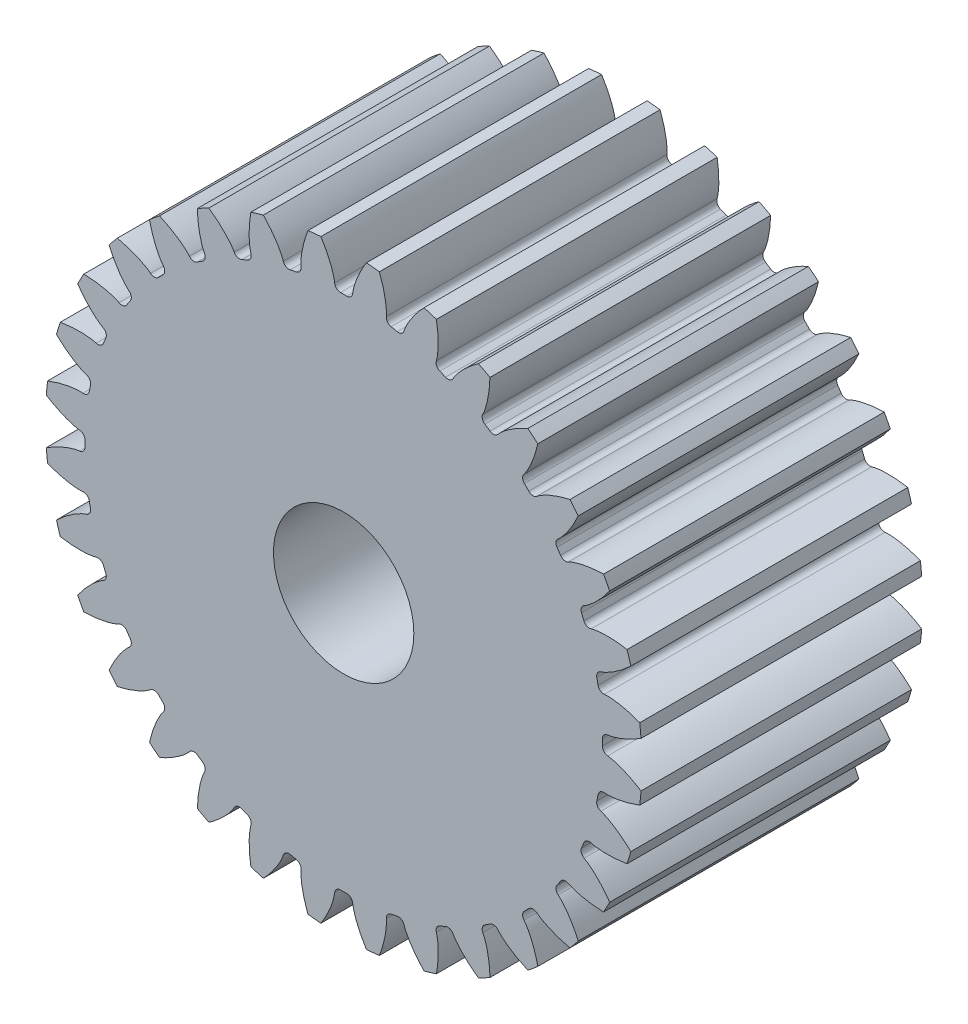
SolidWorks part; units mm, degrees
material "Plain Carbon Steel"
ref_plane "Front Plane" through (0, 0, 0) normal (0, 0, 1) x (1, 0, 0)
ref_plane "Top Plane" through (0, 0, 0) normal (0, 1, 0) x (1, 0, 0)
ref_plane "Right Plane" through (0, 0, 0) normal (1, 0, 0) x (0, 0, -1)
sketch "Sketch1" plane through (0, 0, 0) normal (0, 0, 1) x (1, 0, 0)
  line L0 (0, 0) -> (0, 12.7) construction
  line L1 (-4.0817, 14.1856) -> (4.0817, 11.2144) construction
  circle A0 centre (0, 0) radius 11.7078 construction
  circle A1 centre (0, 0) radius 13.4938 construction
  circle A2 centre (0, 0) radius 12.7 construction
  circle A3 centre (0, 0) radius 11.9341 construction
  point P8 (406.4, 0)
  point P13 (406.4, 0)
  dimension "OD | Outside Diameter" = 26.9875
  dimension "Root Diameter" = 23.4156
  dimension "Gear Pitch Diameter" = 25.4
  dimension "Base Diameter" = 23.8682
  dimension "Pressure Angle" = 20
  dimension "Number of Teeth" = 812.8
  dimension "Gear Pitch | Diametral Pitch" = 812.8
sketch "Sketch2" plane through (0, 0, 0) normal (1, 0, 0) x (0, 0, -1)
  line L0 (-6.35, 0) -> (6.35, 0) construction
  point P2 (7.1437, 0)
  point P5 (13.8906, 0)
  point P6 (-7.1437, 0)
  dimension "Length" = 12.7
  dimension "D1" = 13.4937
  dimension "D2" = 20.2406
  dimension "D3" = 13.4937
sketch "Sketch3" plane through (0, 0, 0) normal (0, 0, 1) x (1, 0, 0)
  circle A0 centre (0, 0) radius 13.4938
  circle A1 centre (0, 0) radius 13.4937 construction
extrude "Boss-Extrude1" add sketch "Sketch3" against normal up to vertex (6.35 mm away) and the other way up to vertex (6.35 mm away) up to point (0, 0, -6.35) other way up to point (0, 0, 6.35)
sketch "Sketch4" plane through (0, 0, 0) normal (0, 0, 1) x (1, 0, 0)
  line L0 (0, 0) -> (11.701, 0.4001) construction
  line L2 (0, 0) -> (11.701, -0.4001) construction
  line L4 (11.701, 0.4001) -> (11.9271, 0.4079)
  line L5 (11.9271, -0.4079) -> (11.701, -0.4001)
  arc A0 (11.701, 0.4001) -> (11.701, -0.4001) centre (0, 0) cw
  arc A3 (13.4545, 1.0288) -> (13.4545, -1.0288) centre (0, 0) cw
  circle A4 centre (0, 0) radius 13.4937 construction
  spline S0 degree 4 poles (11.9271, 0.4079) (11.9296, 0.408) (11.9365, 0.4084) (11.9495, 0.4095) (11.9706, 0.4117) (11.9976, 0.4153) (12.0324, 0.4207) (12.0733, 0.4281) (12.1181, 0.4373) (12.1668, 0.4485) (12.2153, 0.4607) (12.2636, 0.4738) (12.3116, 0.4878) (12.3697, 0.5057) (12.4391, 0.5286) (12.52, 0.5574) (12.6114, 0.5926) (12.7042, 0.631) (12.7953, 0.6709) (12.8869, 0.7137) (12.9752, 0.7568) (13.0666, 0.8041) (13.1507, 0.8491) (13.2444, 0.9022) (13.3199, 0.9459) (13.419, 1.0064) (13.4774, 1.0431) (13.5454, 1.087) (13.5756, 1.107) (13.5941, 1.1193) knots 0 0 0 0 0 0.005377 0.015084 0.028532 0.04661 0.064855 0.092111 0.119476 0.146842 0.174209 0.201575 0.228941 0.256307 0.307035 0.361767 0.4165 0.471232 0.525964 0.580697 0.635429 0.690161 0.744894 0.799626 0.854358 0.909091 0.954545 1 1 1 1 1 construction
  spline S1 degree 4 poles (11.9271, 0.4079) (11.9296, 0.408) (11.9365, 0.4084) (11.9495, 0.4095) (11.9706, 0.4117) (11.9976, 0.4153) (12.0324, 0.4207) (12.0733, 0.4281) (12.1181, 0.4373) (12.1668, 0.4485) (12.2153, 0.4607) (12.2636, 0.4738) (12.3116, 0.4878) (12.3697, 0.5057) (12.4391, 0.5286) (12.52, 0.5574) (12.6114, 0.5926) (12.7042, 0.631) (12.7953, 0.6709) (12.8869, 0.7137) (12.9752, 0.7568) (13.0666, 0.8041) (13.1507, 0.8491) (13.2444, 0.9022) (13.3199, 0.9459) (13.3975, 0.9933) (13.4352, 1.0167) (13.4545, 1.0288) knots 0 0 0 0 0 0.005377 0.015084 0.028532 0.04661 0.064855 0.092111 0.119476 0.146842 0.174209 0.201575 0.228941 0.256307 0.307035 0.361767 0.4165 0.471232 0.525964 0.580697 0.635429 0.690161 0.744894 0.799626 0.854358 0.909091 0.909091 0.909091 0.909091 0.909091
  spline S2 degree 4 poles (11.9271, -0.4079) (11.9296, -0.408) (11.9365, -0.4084) (11.9495, -0.4095) (11.9706, -0.4117) (11.9976, -0.4153) (12.0324, -0.4207) (12.0733, -0.4281) (12.1181, -0.4373) (12.1668, -0.4485) (12.2153, -0.4607) (12.2636, -0.4738) (12.3116, -0.4878) (12.3697, -0.5057) (12.4391, -0.5286) (12.52, -0.5574) (12.6114, -0.5926) (12.7042, -0.631) (12.7953, -0.6709) (12.8869, -0.7137) (12.9752, -0.7568) (13.0666, -0.8041) (13.1507, -0.8491) (13.2444, -0.9022) (13.3199, -0.9459) (13.419, -1.0064) (13.4774, -1.0431) (13.5454, -1.087) (13.5756, -1.107) (13.5941, -1.1193) knots 0 0 0 0 0 0.005377 0.015084 0.028532 0.04661 0.064855 0.092111 0.119476 0.146842 0.174209 0.201575 0.228941 0.256307 0.307035 0.361767 0.4165 0.471232 0.525964 0.580697 0.635429 0.690161 0.744894 0.799626 0.854358 0.909091 0.954545 1 1 1 1 1 construction
  spline S3 degree 4 poles (11.9271, -0.4079) (11.9296, -0.408) (11.9365, -0.4084) (11.9495, -0.4095) (11.9706, -0.4117) (11.9976, -0.4153) (12.0324, -0.4207) (12.0733, -0.4281) (12.1181, -0.4373) (12.1668, -0.4485) (12.2153, -0.4607) (12.2636, -0.4738) (12.3116, -0.4878) (12.3697, -0.5057) (12.4391, -0.5286) (12.52, -0.5574) (12.6114, -0.5926) (12.7042, -0.631) (12.7953, -0.6709) (12.8869, -0.7137) (12.9752, -0.7568) (13.0666, -0.8041) (13.1507, -0.8491) (13.2444, -0.9022) (13.3199, -0.9459) (13.3975, -0.9933) (13.4352, -1.0167) (13.4545, -1.0288) knots 0 0 0 0 0 0.005377 0.015084 0.028532 0.04661 0.064855 0.092111 0.119476 0.146842 0.174209 0.201575 0.228941 0.256307 0.307035 0.361767 0.4165 0.471232 0.525964 0.580697 0.635429 0.690161 0.744894 0.799626 0.854358 0.909091 0.909091 0.909091 0.909091 0.909091
  dimension "D1" = 23.4156
extrude "Cut-Extrude1" cut sketch "Sketch4" against normal through all both and the other way through all
fillet "Fillet1" radius 0.2663 2 edges at (11.701, -0.4001, 0) (11.701, 0.4001, 0)
pattern_circular "CirPattern1" count 32 over 360 about axis through (0, 0, 6.35) along (0, 0, -1) of "Cut-Extrude1", "Fillet1"
sketch "Sketch5" plane through (0, 0, 6.35) normal (0, 0, 1) x (1, 0, 0)
  point P0 (0, 0)
hole_wizard "1/4 (0.2500) Dowel Hole1" positions "Sketch5" profile "Sketch6" hole size "1/4" standard "ANSI Inch" end condition through all
sketch "Sketch6" plane through (0, 0, 6.35) normal (1, 0, 0) x (0, -1, 0)
  line L0 (0, 0) -> (0, 12.7)
  line L1 (0, 12.7) -> (3.175, 12.7)
  line L2 (3.175, 12.7) -> (3.175, 0)
  line L5 (3.175, 0) -> (0, 0)
  line L11 (0, -6.35) -> (0, 107.95) construction
  dimension "Thru Hole Dia." = 6.35
  dimension "Thru Hole Depth" = 12.7
equation "\"Root Diameter@Sketch1\"=\"Root Diameter\""
equation "\"OD | Outside Diameter@Sketch1\"=\"Outside Diameter\""
equation "\"D1@CirPattern1\"=\"Number of Teeth\""
equation "\"Diametral Pitch\"=32"
equation "\"Number of Teeth\"= 32"
equation "\"Pressure Angle\"=20"
equation "\"Pitch Diameter\"= \"Number of Teeth\" / \"Diametral Pitch\""
equation "\"Base Diameter\"= \"Pitch Diameter\" * cos ( \"Pressure Angle\" )"
equation "\"Outside Diameter\"= ( \"Number of Teeth\" + 2 ) / \"Diametral Pitch\""
equation "\"Dedendum\"= 1.25 / \"Diametral Pitch\""
equation "\"Root Diameter\"= \"Pitch Diameter\" - ( 2 * \"Dedendum\" )"
equation "\"Pitch Angle\"= 360deg / \"Number of Teeth\""
equation "\"Alpha\"= sqr ( \"Pitch Diameter\" ^ 2 - \"Base Diameter\" ^ 2 ) / \"Base Diameter\" * 180 / PI - \"Pressure Angle\""
equation "\"Beta\"= ( \"Pitch Angle\" / 4 - \"Alpha\" )"
equation "\"Phi\"= sqr ( ( \"Outside Diameter\" / 2 ) ^ 2 - ( \"Base Diameter\" / 2 ) ^ 2 ) / ( \"Base Diameter\" / 2 )"
equation "\"Addendum\"= 1 / \"Diametral Pitch\""
equation "\"WorkingDepth\"= 2 / \"Diametral Pitch\""
equation "\"WholeDepth\"= 2.25 / \"Diametral Pitch\""
equation "\"Clearance\"= 0.25 / \"Diametral Pitch\""
equation "\"ToothThickness\"= ( pi * 2 ) / \"Diametral Pitch\""
equation "\"CircularPitch\"= pi / \"Diametral Pitch\""
equation "\"Number of Teeth@Sketch1\"=\"Number of Teeth\""
equation "\"Gear Pitch | Diametral Pitch@Sketch1\"=\"Diametral Pitch\""
equation "\"Pressure Angle@Sketch1\"=\"Pressure Angle\""
equation "\"Gear Pitch Diameter@Sketch1\"=\"Pitch Diameter\""
equation "\"Base Diameter@Sketch1\"=\"Base Diameter\""
equation "\"Fillet\"= \"Clearance\" * cos ( \"Pressure Angle\" ) * tan ( ( 90 + \"Pressure Angle\" ) / 2 )"
equation "\"D1@Fillet1\"=\"Fillet\""
equation "\"D1@Sketch4\"=if( \"Base Diameter\">\"Root Diameter\",\"Root Diameter\",\"Base Diameter\"-.00001)"
equation "\"D1@Sketch2\"=\"OD | Outside Diameter@Sketch1\"*2*0.5*0.5"
equation "\"D2@Sketch2\"=\"D1@Sketch2\"*1.5"
equation "\"D3@Sketch2\"=\"D1@Sketch2\""
equation "\"Length\"= .5in"
equation "\"Length@Sketch2\"= \"Length\""
